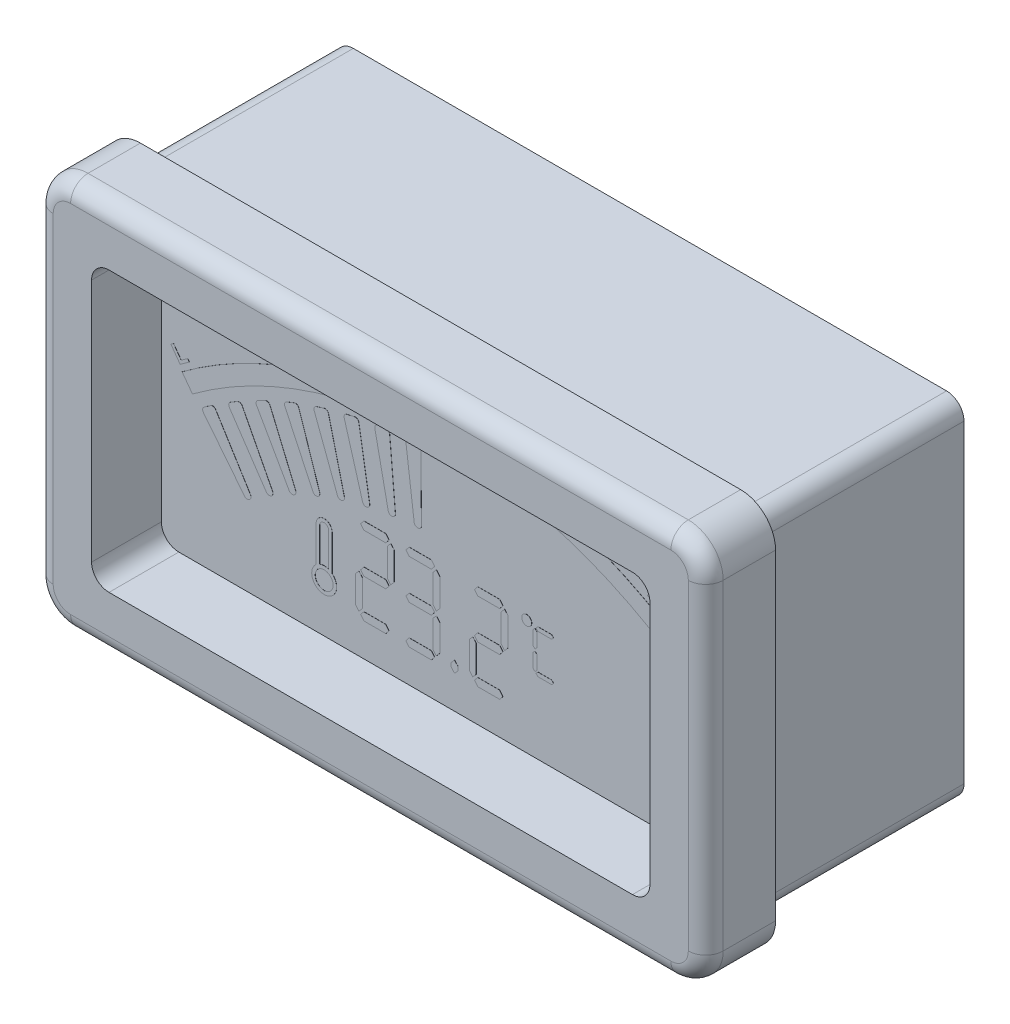
SolidWorks part; units mm, degrees
ref_plane "Plan de face" through (0, 0, 0) normal (0, 0, 1) x (1, 0, 0)
ref_plane "Plan de dessus" through (0, 0, 0) normal (0, 1, 0) x (1, 0, 0)
ref_plane "Plan de droite" through (0, 0, 0) normal (1, 0, 0) x (0, 0, -1)
sketch "Esquisse1" plane through (0, 0, 0) normal (0, 0, 1) x (1, 0, 0)
  line L1 (21.5, 14) -> (-21.5, 14)
  line L2 (24, 11.5) -> (24, -11.5)
  line L3 (21.5, -14) -> (-21.5, -14)
  line L4 (-24, 11.5) -> (-24, -11.5)
  line L5 (24, 14) -> (-24, -14) construction
  line L6 (24, -14) -> (-24, 14) construction
  line L7 (18.75, -10) -> (-18.75, -10)
  line L8 (20, -8.75) -> (20, 8.75)
  line L9 (18.75, 10) -> (-18.75, 10)
  line L10 (-20, -8.75) -> (-20, 8.75)
  line L11 (20, -10) -> (-20, 10) construction
  line L12 (20, 10) -> (-20, -10) construction
  arc A0 (21.5, 14) -> (24, 11.5) centre (21.5, 11.5) cw
  arc A1 (24, -11.5) -> (21.5, -14) centre (21.5, -11.5) cw
  arc A2 (-21.5, -14) -> (-24, -11.5) centre (-21.5, -11.5) cw
  arc A3 (-21.5, 14) -> (-24, 11.5) centre (-21.5, 11.5) ccw
  arc A4 (20, 8.75) -> (18.75, 10) centre (18.75, 8.75) ccw
  arc A5 (18.75, -10) -> (20, -8.75) centre (18.75, -8.75) ccw
  arc A6 (-18.75, -10) -> (-20, -8.75) centre (-18.75, -8.75) cw
  arc A7 (-18.75, 10) -> (-20, 8.75) centre (-18.75, 8.75) ccw
  point P0 (0, 0)
  point P18 (0, 0)
  dimension "D1" = 2.5
  dimension "D2" = 1.25
extrude "Bezzle" add sketch "Esquisse1" along normal blind 5
fillet "Fillet" radius 1.25 8 edges at (23.2678, 13.2678, 5) (24, 0, 5) (23.2678, -13.2678, 5) (0, -14, 5) (-23.2678, -13.2678, 5) (-24, 0, 5) (-23.2678, 13.2678, 5) (0, 14, 5)
ref_plane "Plane" through (0, 0, 0) normal (0, 0, -1) x (-1, 0, 0)
sketch "Esquisse2" plane through (0, 0, 0) normal (0, 0, -1) x (-1, 0, 0)
  line L6 (21.25, -12.5) -> (-21.25, -12.5)
  line L7 (22.5, -11.25) -> (22.5, 11.25)
  line L8 (21.25, 12.5) -> (-21.25, 12.5)
  line L9 (-22.5, -11.25) -> (-22.5, 11.25)
  line L10 (22.5, -12.5) -> (-22.5, 12.5) construction
  line L11 (22.5, 12.5) -> (-22.5, -12.5) construction
  arc A4 (22.5, 11.25) -> (21.25, 12.5) centre (21.25, 11.25) ccw
  arc A5 (21.25, -12.5) -> (22.5, -11.25) centre (21.25, -11.25) ccw
  arc A6 (-21.25, -12.5) -> (-22.5, -11.25) centre (-21.25, -11.25) cw
  arc A7 (-21.25, 12.5) -> (-22.5, 11.25) centre (-21.25, 11.25) ccw
  point P0 (0, 0)
  point P17 (0, 0)
  dimension "D1" = 25
  dimension "D2" = 1.25
  dimension "D3" = 45
extrude "Body" add sketch "Esquisse2" along normal blind 15 separate body
sketch "Sketch1" plane through (0, 0, 0) normal (0, 0, 1) x (1, 0, 0)
  line L0 (-338.9678, 86.5845) -> (-51.6345, 86.5845) construction
sketch "Sketch2" plane through (0, 0, 0) normal (0, 0, 1) x (1, 0, 0)
  line L0 (0, -23.6644) -> (-18.5063, 1.3106)
  line L1 (0, -23.6644) -> (-5.991, 6.8371)
  line L2 (0, -23.6644) -> (0, 7.4199) construction
  line L3 (0, -23.6644) -> (5.991, 6.8371)
  line L4 (0, -23.6644) -> (18.5063, 1.3106)
  line L5 (0, -23.6644) -> (-16.6948, 0.0737) construction
  line L6 (-8.3274, -5.9258) -> (-8.3274, -3.2803) construction
  line L7 (-8.8983, -5.8403) -> (-8.8983, -3.2803)
  line L8 (-7.7566, -5.8403) -> (-7.7566, -3.2803)
  line L9 (-8.0066, -5.6932) -> (-8.0066, -3.2803)
  line L10 (-8.6483, -5.6932) -> (-8.6483, -3.2803)
  line L11 (-8.0066, -5.8403) -> (-8.0066, -3.2803) construction
  line L12 (-8.6483, -5.8403) -> (-8.6483, -3.2803) construction
  line L13 (-17.1427, -0.2477) -> (-13.8845, -4.3488)
  line L14 (-16.2409, 0.3865) -> (-13.4831, -4.0665)
  circle A0 centre (0, -23.6644) radius 29.8343
  circle A1 centre (0, -23.6644) radius 31.0843
  circle A2 centre (0, -23.6644) radius 29.0209
  circle A3 centre (0, -23.6644) radius 23.7881
  arc A4 (-8.8983, -5.8403) -> (-7.7566, -5.8403) centre (-8.3274, -6.5246) ccw
  arc A6 (-7.7566, -3.2803) -> (-8.8983, -3.2803) centre (-8.3274, -3.2803) ccw
  circle A7 centre (-8.3274, -6.5246) radius 0.6411
  arc A8 (-8.0066, -3.2803) -> (-8.6483, -3.2803) centre (-8.3274, -3.2803) ccw
  circle A9 centre (-8.3274, -6.5246) radius 0.8911 construction
  arc A10 (-8.0066, -5.6932) -> (-8.6483, -5.6932) centre (-8.3274, -6.5246) ccw
  point P16 (-8.3274, -4.6031)
  dimension "D1" = 1.25
  dimension "D2" = 0.25
  dimension "D3" = 0.25
extrude "Boss-Extrude1" add sketch "Sketch2" along normal blind 0.01 separate body contours L1 A1 L0 A0 region at (-12.205, 3.975, 0)
extrude "Boss-Extrude2" add sketch "Sketch2<3>" along normal blind 0.01 separate body contours L3 A1 L1 A0 region at (0, 6.6085, 0)
sketch "Sketch2<3>" plane through (0, 0, 0) normal (0, 0, 1) x (1, 0, 0) same geometry as "Sketch2"
extrude "Boss-Extrude3" add sketch "Sketch2<4>" along normal blind 0.01 separate body contours L4 A1 L3 A0 region at (12.205, 3.975, 0)
sketch "Sketch2<4>" plane through (0, 0, 0) normal (0, 0, 1) x (1, 0, 0) same geometry as "Sketch2"
extrude "Boss-Extrude4" add sketch "Sketch2<5>" along normal blind 0.01 separate body contours A3 L14 A2 L13 region at (-15.3817, -1.7934, 0)
sketch "Sketch2<5>" plane through (0, 0, 0) normal (0, 0, 1) x (1, 0, 0) same geometry as "Sketch2"
extrude "Boss-Extrude5" add sketch "Sketch2<6>" along normal blind 0.01 separate body contours L8 A6 L7 A4 A7 L9 A10 L10 A8 region at (-8.848, -4.5603, 0)
sketch "Sketch2<6>" plane through (0, 0, 0) normal (0, 0, 1) x (1, 0, 0) same geometry as "Sketch2"
fillet "Fillet1" radius 0.25 4 edges at (-13.4831, -4.0665, 0.005) (-13.8845, -4.3488, 0.005) (-16.2409, 0.3865, 0.005) (-17.1427, -0.2477, 0.005)
ref_axis "Axis1" through (0, -23.6644, 0) along (0, 0, 1)
pattern_circular "CirPattern1" count 8 over 31.25 about axis through (0, -23.6644, 0) along (0, 0, 1) reverse direction yes of bodies 106
sketch "Sketch3" plane through (0, 0, 0) normal (0, 0, 1) x (1, 0, 0)
  line L4 (17.7621, 0.3063) -> (18.5063, 1.3106) construction
  arc A6 (-6.0681, 7.2296) -> (-18.7444, 1.632) centre (0, -23.6644) ccw
  arc A7 (18.7444, 1.632) -> (-18.7444, 1.632) centre (0, -23.6644) ccw construction
  text T0 "L             -20                  20                  60               100   H" font "Arial" height 1.15
  dimension "D1" = 0.4
extrude "Boss-Extrude6" add sketch "Sketch3" along normal blind 0.01 separate body
sketch "Sketch4" plane through (0, 0, 0) normal (0, 0, 1) x (1, 0, 0)
  line L0 (-6.4912, -7.6347) -> (4.9184, -7.6347) construction
  line L1 (6.3887, -4.861) -> (9.7042, -4.861) construction
  line L2 (-6.0833, -6.9285) -> (-6.0833, -4.9999)
  line L3 (-6.0833, -4.9999) -> (-5.8385, -4.7208)
  line L4 (-5.8385, -4.7208) -> (-5.5938, -4.9999)
  line L5 (-5.5938, -4.9999) -> (-5.5938, -6.9285)
  line L6 (-5.5938, -6.9285) -> (-5.8385, -7.2076)
  line L7 (-5.8385, -7.2076) -> (-6.0833, -6.9285)
  line L8 (-5.7149, -7.3517) -> (-5.4804, -7.0636)
  line L9 (-5.4804, -7.0636) -> (-3.9125, -7.0636)
  line L10 (-3.9125, -7.0636) -> (-3.678, -7.3517)
  line L11 (-3.678, -7.3517) -> (-3.9125, -7.6347)
  line L12 (-3.9125, -7.6347) -> (-5.4804, -7.6347)
  line L13 (-5.4804, -7.6347) -> (-5.7149, -7.3517)
  line L14 (-5.7149, -4.5755) -> (-5.4804, -4.2899)
  line L15 (-5.4804, -4.2899) -> (-3.9125, -4.2899)
  line L16 (-3.9125, -4.2899) -> (-3.678, -4.5755)
  line L17 (-3.678, -4.5755) -> (-3.9125, -4.861)
  line L18 (-3.9125, -4.861) -> (-5.4804, -4.861)
  line L19 (-5.4804, -4.861) -> (-5.7149, -4.5755)
  line L20 (-5.7149, -1.7202) -> (-5.4804, -1.4347)
  line L21 (-5.4804, -1.4347) -> (-3.9125, -1.4347)
  line L22 (-3.9125, -1.4347) -> (-3.678, -1.7202)
  line L23 (-3.678, -1.7202) -> (-3.9125, -2.0057)
  line L24 (-3.9125, -2.0057) -> (-5.4804, -2.0057)
  line L25 (-5.4804, -2.0057) -> (-5.7149, -1.7202)
  line L26 (-3.7991, -4.1459) -> (-3.7991, -2.1498)
  line L27 (-3.7991, -2.1498) -> (-3.5543, -1.8655)
  line L28 (-3.5543, -1.8655) -> (-3.3096, -2.1498)
  line L29 (-3.3096, -2.1498) -> (-3.3096, -4.1459)
  line L30 (-3.3096, -4.1459) -> (-3.5543, -4.4301)
  line L31 (-3.5543, -4.4301) -> (-3.7991, -4.1459)
  line L32 (-2.4696, -7.3517) -> (-2.2414, -7.0636)
  line L33 (-2.2414, -7.0636) -> (-0.643, -7.0636)
  line L34 (-0.643, -7.0636) -> (-0.4148, -7.3517)
  line L35 (-0.4148, -7.3517) -> (-0.643, -7.6347)
  line L36 (-0.643, -7.6347) -> (-2.2414, -7.6347)
  line L37 (-2.2414, -7.6347) -> (-2.4696, -7.3517)
  line L38 (-2.4696, -4.5755) -> (-2.2414, -4.2899)
  line L39 (-2.2414, -4.2899) -> (-0.643, -4.2899)
  line L40 (-0.643, -4.2899) -> (-0.4148, -4.5755)
  line L41 (-0.4148, -4.5755) -> (-0.643, -4.861)
  line L42 (-0.643, -4.861) -> (-2.2414, -4.861)
  line L43 (-2.2414, -4.861) -> (-2.4696, -4.5755)
  line L44 (-2.4696, -1.7202) -> (-2.2414, -1.4347)
  line L45 (-2.2414, -1.4347) -> (-0.643, -1.4347)
  line L46 (-0.643, -1.4347) -> (-0.4148, -1.7202)
  line L47 (-0.4148, -1.7202) -> (-0.643, -2.0057)
  line L48 (-0.643, -2.0057) -> (-2.2414, -2.0057)
  line L49 (-2.2414, -2.0057) -> (-2.4696, -1.7202)
  line L50 (-0.5359, -6.9285) -> (-0.5359, -4.9999)
  line L51 (-0.5359, -4.9999) -> (-0.2912, -4.7208)
  line L52 (-0.2912, -4.7208) -> (-0.0464, -4.9999)
  line L53 (-0.0464, -4.9999) -> (-0.0464, -6.9285)
  line L54 (-0.0464, -6.9285) -> (-0.2912, -7.2076)
  line L55 (-0.2912, -7.2076) -> (-0.5359, -6.9285)
  line L56 (-0.5359, -4.1459) -> (-0.5359, -2.1498)
  line L57 (-0.5359, -2.1498) -> (-0.2912, -1.8655)
  line L58 (-0.2912, -1.8655) -> (-0.0464, -2.1498)
  line L59 (-0.0464, -2.1498) -> (-0.0464, -4.1459)
  line L60 (-0.0464, -4.1459) -> (-0.2912, -4.4301)
  line L61 (-0.2912, -4.4301) -> (-0.5359, -4.1459)
  line L62 (0.7694, -7.367) -> (0.7694, -7.0904)
  line L63 (0.7694, -7.0904) -> (1.0141, -6.8189)
  line L64 (1.0141, -6.8189) -> (1.2588, -7.0904)
  line L65 (1.2588, -7.0904) -> (1.2588, -7.367)
  line L66 (1.2588, -7.367) -> (1.0141, -7.6347)
  line L67 (1.0141, -7.6347) -> (0.7694, -7.367)
  line L68 (2.0746, -6.9285) -> (2.0746, -4.9999)
  line L69 (2.0746, -4.9999) -> (2.3194, -4.7208)
  line L70 (2.3194, -4.7208) -> (2.5641, -4.9999)
  line L71 (2.5641, -4.9999) -> (2.5641, -6.9285)
  line L72 (2.5641, -6.9285) -> (2.3194, -7.2076)
  line L73 (2.3194, -7.2076) -> (2.0746, -6.9285)
  line L74 (2.443, -7.3517) -> (2.6775, -7.0636)
  line L75 (2.6775, -7.0636) -> (4.2454, -7.0636)
  line L76 (4.2454, -7.0636) -> (4.4799, -7.3517)
  line L77 (4.4799, -7.3517) -> (4.2454, -7.6347)
  line L78 (4.2454, -7.6347) -> (2.6775, -7.6347)
  line L79 (2.6775, -7.6347) -> (2.443, -7.3517)
  line L80 (2.443, -4.5755) -> (2.6775, -4.2899)
  line L81 (2.6775, -4.2899) -> (4.2454, -4.2899)
  line L82 (4.2454, -4.2899) -> (4.4799, -4.5755)
  line L83 (4.4799, -4.5755) -> (4.2454, -4.861)
  line L84 (4.2454, -4.861) -> (2.6775, -4.861)
  line L85 (2.6775, -4.861) -> (2.443, -4.5755)
  line L86 (2.443, -1.7202) -> (2.6775, -1.4347)
  line L87 (2.6775, -1.4347) -> (4.2454, -1.4347)
  line L88 (4.2454, -1.4347) -> (4.4799, -1.7202)
  line L89 (4.4799, -1.7202) -> (4.2454, -2.0057)
  line L90 (4.2454, -2.0057) -> (2.6775, -2.0057)
  line L91 (2.6775, -2.0057) -> (2.443, -1.7202)
  line L92 (4.3588, -4.1459) -> (4.3588, -2.1498)
  line L93 (4.3588, -2.1498) -> (4.6036, -1.8655)
  line L94 (4.6036, -1.8655) -> (4.8483, -2.1498)
  line L95 (4.8483, -2.1498) -> (4.8483, -4.1459)
  line L96 (4.8483, -4.1459) -> (4.6036, -4.4301)
  line L97 (4.6036, -4.4301) -> (4.3588, -4.1459)
  line L98 (6.6335, -4.5041) -> (6.6335, -3.5213)
  line L99 (6.6335, -3.5213) -> (6.7762, -3.3811)
  line L100 (6.7762, -3.3811) -> (6.919, -3.5213)
  line L101 (6.919, -3.5213) -> (6.919, -4.5041)
  line L102 (6.919, -4.5041) -> (6.7762, -4.6456)
  line L103 (6.7762, -4.6456) -> (6.6335, -4.5041)
  line L104 (6.6335, -3.0987) -> (6.6335, -2.1153)
  line L105 (6.6335, -2.1153) -> (6.7762, -1.9745)
  line L106 (6.7762, -1.9745) -> (6.919, -2.1153)
  line L107 (6.919, -2.1153) -> (6.919, -3.0987)
  line L108 (6.919, -3.0987) -> (6.7762, -3.2409)
  line L109 (6.7762, -3.2409) -> (6.6335, -3.0987)
  line L110 (6.8489, -4.7182) -> (6.9885, -4.5755)
  line L111 (6.9885, -4.5755) -> (7.9693, -4.5755)
  line L112 (7.9693, -4.5755) -> (8.1096, -4.7182)
  line L113 (8.1096, -4.7182) -> (7.9693, -4.861)
  line L114 (7.9693, -4.861) -> (6.9885, -4.861)
  line L115 (6.9885, -4.861) -> (6.8489, -4.7182)
  line L116 (6.8489, -1.905) -> (6.9885, -1.761)
  line L117 (6.9885, -1.761) -> (7.9693, -1.761)
  line L118 (7.9693, -1.761) -> (8.1096, -1.905)
  line L119 (8.1096, -1.905) -> (7.9693, -2.0465)
  line L120 (7.9693, -2.0465) -> (6.9885, -2.0465)
  line L121 (6.9885, -2.0465) -> (6.8489, -1.905)
  circle A0 centre (6.1839, -1.761) radius 0.3554
extrude "Boss-Extrude7" add sketch "Sketch4" along normal blind 0.01 separate body
